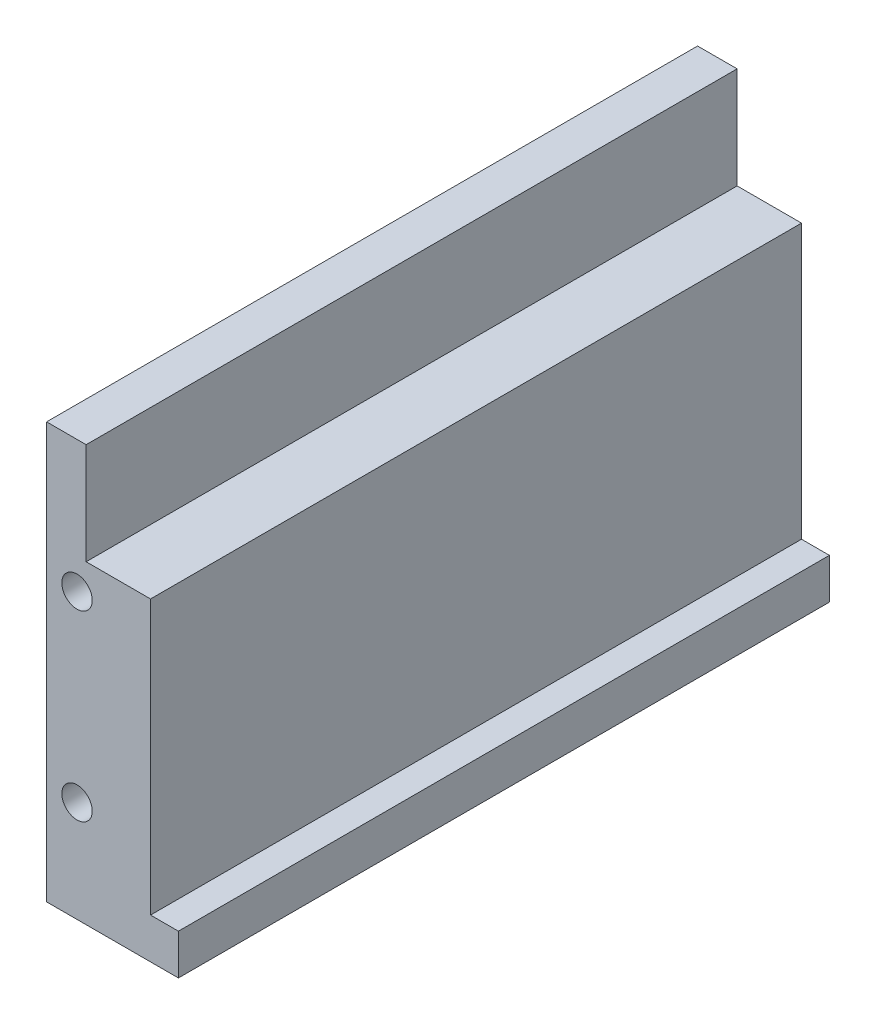
SolidWorks part; units mm, degrees
ref_plane "Front Plane" through (0, 0, 0) normal (0, 0, 1) x (1, 0, 0)
ref_plane "Top Plane" through (0, 0, 0) normal (0, 1, 0) x (1, 0, 0)
ref_plane "Right Plane" through (0, 0, 0) normal (1, 0, 0) x (0, 0, -1)
sketch "Sketch1" plane through (0, 0, 0) normal (0, 0, 1) x (1, 0, 0)
  line L8 (0, 0) -> (0, 41)
  line L9 (0, 41) -> (3.9, 41)
  line L10 (3.9, 41) -> (3.9, 31)
  line L11 (3.9, 31) -> (10.25, 31)
  line L12 (10.25, 31) -> (10.25, 4)
  line L15 (10.25, 4) -> (13, 4)
  line L16 (13, 4) -> (13, 0)
  line L17 (13, 0) -> (0, 0)
  point P2 (10.3, 4)
  point P3 (9.9536, 4)
  dimension "D1" = 10
  dimension "D2" = 41
  dimension "D3" = 4
  dimension "D4" = 2.75
  dimension "D5" = 13
  dimension "D6" = 9.1
extrude "Boss-Extrude1" add sketch "Sketch1" along normal blind 64.2
ref_plane "Plane1" through (0, 0, 32.1) normal (0, 0, 1) x (1, 0, 0)
sketch "Sketch2" plane through (0, 0, 64.2) normal (0, 0, 1) x (1, 0, 0)
  line L0 (3, 41) -> (3, 0) construction
  line L1 (3.9, 41) -> (0, 41) construction
  line L2 (0, 0) -> (13, 0) construction
  line L3 (0, 41) -> (0, 0) construction
  circle A0 centre (3, 28) radius 1.5
  circle A1 centre (3, 10) radius 1.5
  dimension "D2" = 3
  dimension "D1" = 3
  dimension "D3" = 13
  dimension "D4" = 10
extrude "Cut-Extrude1" cut sketch "Sketch2" against normal blind 5
mirror "Mirror1" about plane through (0, 0, 32.1) normal (0, 0, 1) of "Cut-Extrude1"
